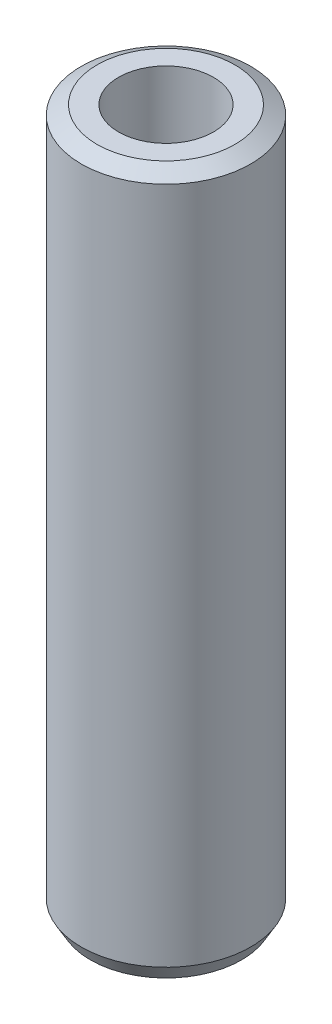
SolidWorks part; units mm, degrees
ref_plane "Front Plane" through (0, 0, 0) normal (0, 0, 1) x (1, 0, 0)
ref_plane "Top Plane" through (0, 0, 0) normal (0, 1, 0) x (1, 0, 0)
ref_plane "Right Plane" through (0, 0, 0) normal (1, 0, 0) x (0, 0, -1)
sketch "Sketch1" plane through (0, 0, 0) normal (0, 1, 0) x (1, 0, 0)
  circle A0 centre (0, 0) radius 15
  dimension "SHAFT_OD" = 30
extrude "Boss-Extrude1" add sketch "Sketch1" along normal blind 124.4921
sketch "Sketch2" plane through (0, 0, 0) normal (0, 1, 0) x (1, 0, 0)
  circle A0 centre (0, 0) radius 8.4039
  dimension "BORE_D" = 16.8078
extrude "Cut-Extrude1" cut sketch "Sketch2" along normal through all
chamfer "Chamfer1" distance 1.6084 angle 60 2 edges at (0, 124.4921, 15) (0, 0, 15) first distance on face at (0, 124.4921, 15) first distance on face at (0, 0, 8.4039)
